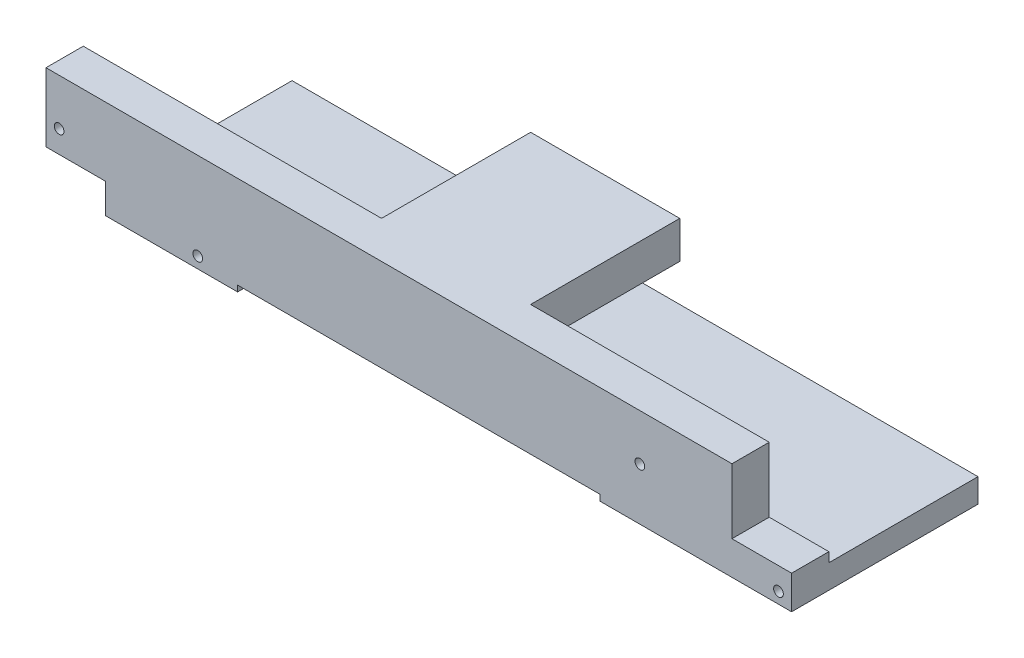
SolidWorks part; units mm, degrees
ref_plane "Front Plane" through (0, 0, 0) normal (0, 0, 1) x (1, 0, 0)
ref_plane "Top Plane" through (0, 0, 0) normal (0, 1, 0) x (1, 0, 0)
ref_plane "Right Plane" through (0, 0, 0) normal (1, 0, 0) x (0, 0, -1)
sketch "Sketch1" plane through (0, 0, 0) normal (0, 1, 0) x (1, 0, 0)
  line L1 (-63.5, -15.875) -> (63.5, -15.875)
  line L2 (-63.5, -15.875) -> (-63.5, 15.875)
  line L3 (-63.5, 15.875) -> (63.5, 15.875)
  line L4 (63.5, -15.875) -> (63.5, 15.875)
  line L5 (-63.5, -15.875) -> (63.5, 15.875) construction
  line L6 (-63.5, 15.875) -> (63.5, -15.875) construction
  point P0 (0, 0)
  dimension "D1" = 31.75
  dimension "D2" = 127
extrude "Boss-Extrude1" add sketch "Sketch1" along normal blind 16.764
sketch "Sketch2" plane through (-63.5, 0, 0) normal (-1, 0, 0) x (0, 0, 1)
  line L0 (-15.875, 16.764) -> (-15.875, 0) construction
  line L1 (-15.875, 10.414) -> (9.525, 10.414)
  line L2 (-15.875, 10.414) -> (-15.875, 4.064)
  line L3 (-15.875, 4.064) -> (9.525, 4.064)
  line L4 (9.525, 10.414) -> (9.525, 4.064)
  dimension "D1" = 6.35
  dimension "D2" = 25.4
  dimension "D3" = 4.064
extrude "Cut-Extrude1" cut sketch "Sketch2" against normal up to surface (127 mm away) up to face at (63.5, 8.382, 0)
sketch "Sketch3" plane through (-63.5, 0, 0) normal (-1, 0, 0) x (0, 0, 1)
  line L0 (9.525, 10.414) -> (-15.875, 10.414) construction
  line L1 (-15.875, 16.764) -> (9.525, 16.764)
  line L2 (-15.875, 16.764) -> (-15.875, 10.414)
  line L3 (-15.875, 10.414) -> (9.525, 10.414)
  line L4 (9.525, 16.764) -> (9.525, 10.414)
  dimension "D1" = 25.4
extrude "Cut-Extrude2" cut sketch "Sketch3" against normal blind 50.8
mirror "Mirror1" about plane through (0, 0, 0) normal (1, 0, 0) of "Cut-Extrude2"
sketch "Sketch5" plane through (0, 0, 0) normal (0, -1, 0) x (1, 0, 0)
  line L0 (-27.9908, 1.2954) -> (27.9908, 1.2954) construction
  line L1 (-63.5, 15.875) -> (63.5, 15.875) construction
  line L3 (-30.861, 15.875) -> (30.861, 15.875)
  line L4 (-30.861, 15.875) -> (-30.861, -1.2446)
  line L5 (-30.861, -1.2446) -> (30.861, -1.2446)
  line L6 (30.861, 15.875) -> (30.861, -1.2446)
  circle A0 centre (-27.9908, 1.2954) radius 0.8192
  circle A1 centre (27.9908, 1.2954) radius 0.8192
  point P0 (-27.9908, 1.2954)
  point P1 (27.9908, 1.2954)
  point P2 (0, 1.2954)
  point P12 (0, -1.2446)
  point P18 (0, -1.2446)
  line M3 (63.5, 15.875) -> (-63.5, 15.875)
  dimension "D5" = 1.6383
  dimension "D6" = 1.6383
  dimension "D1" = 2.54
  dimension "D2" = 55.9816
  dimension "D3" = 17.1196
  dimension "D4" = 61.722
extrude "Cut-Extrude3" cut sketch "Sketch5" against normal blind 1.016 contours L6 L4 L5 A0 A1 M3 | A0 | A1 region at (0, 0, 7.3393) region at (-27.9908, 0, 1.2954) region at (27.9908, 0, 1.2954)
extrude "Cut-Extrude4" cut sketch "Sketch5<3>" against normal through all contours A0 | A1 region at (-27.9908, 0, 1.2954) region at (27.9908, 0, 1.2954)
sketch "Sketch5<3>" plane through (0, 0, 0) normal (0, -1, 0) x (1, 0, 0) same geometry as "Sketch5"
sketch "Sketch6" plane through (0, 0, 15.875) normal (0, 0, 1) x (1, 0, 0)
  line L0 (-63.5, 0) -> (-30.861, 0) construction
  line L1 (-63.5, 10.7823) -> (-36.5379, 10.7823)
  line L2 (-63.5, 10.7823) -> (-63.5, 0)
  line L3 (-63.5, 0) -> (-36.5379, 0)
  line L4 (-36.5379, 10.7823) -> (-36.5379, 0)
  line L5 (-61.2648, 8.8773) -> (-37.6555, 8.8773) construction
  line L6 (-61.2648, 8.8773) -> (-61.2648, 1.905) construction
  line L7 (-61.2648, 1.905) -> (-37.6555, 1.905) construction
  line L8 (-37.6555, 8.8773) -> (-37.6555, 1.905) construction
  line L9 (-63.5, 16.764) -> (-63.5, 0) construction
  line L10 (36.5379, 10.7823) -> (63.5, 10.7823)
  line L11 (-36.5379, 10.7823) -> (-46.6979, 10.7823)
  line L12 (-36.5379, 10.7823) -> (-36.5379, 5.7023)
  line L13 (-36.5379, 5.7023) -> (-46.6979, 5.7023)
  line L14 (-46.6979, 10.7823) -> (-46.6979, 5.7023)
  line L15 (-63.5, 0) -> (-53.34, 0)
  line L16 (-63.5, 0) -> (-63.5, 5.08)
  line L17 (-63.5, 5.08) -> (-53.34, 5.08)
  line L18 (-53.34, 0) -> (-53.34, 5.08)
  line L19 (36.5379, 10.7823) -> (36.5379, 0)
  line L20 (36.5379, 0) -> (63.5, 0)
  line L21 (63.5, 10.7823) -> (63.5, 0)
  line L22 (37.6555, 8.8773) -> (61.2648, 8.8773) construction
  line L23 (37.6555, 8.8773) -> (37.6555, 1.905) construction
  line L24 (37.6555, 1.905) -> (61.2648, 1.905) construction
  line L25 (61.2648, 8.8773) -> (61.2648, 1.905) construction
  line L26 (63.5, 10.7823) -> (53.34, 10.7823)
  line L27 (63.5, 10.7823) -> (63.5, 5.7023)
  line L28 (63.5, 5.7023) -> (53.34, 5.7023)
  line L29 (53.34, 10.7823) -> (53.34, 5.7023)
  line L30 (36.5379, 0) -> (46.6979, 0)
  line L31 (36.5379, 0) -> (36.5379, 5.08)
  line L32 (36.5379, 5.08) -> (46.6979, 5.08)
  line L33 (46.6979, 0) -> (46.6979, 5.08)
  line L34 (30.861, 0) -> (63.5, 0) construction
  line L35 (63.5, 16.764) -> (63.5, 0) construction
  line L37 (53.34, 10.7823) -> (63.5, 10.7823)
  line L38 (53.34, 10.7823) -> (53.34, 16.764)
  line L39 (53.34, 16.764) -> (63.5, 16.764)
  line L40 (63.5, 10.7823) -> (63.5, 16.764)
  circle A0 centre (-61.2648, 8.8773) radius 0.8255
  circle A1 centre (-37.6555, 8.8773) radius 0.8255
  circle A2 centre (-37.6555, 1.905) radius 0.8255
  circle A3 centre (-61.2648, 1.905) radius 0.8255
  circle A4 centre (37.6555, 8.8773) radius 0.8255
  circle A5 centre (61.2648, 8.8773) radius 0.8255
  circle A6 centre (61.2648, 1.905) radius 0.8255
  circle A7 centre (37.6555, 1.905) radius 0.8255
  line M11 (63.5, 0) -> (63.5, 16.764)
  line M12 (63.5, 16.764) -> (-63.5, 16.764)
  line M14 (-63.5, 0) -> (-30.861, 0)
  dimension "D7" = 1.651
  dimension "D8" = 1.651
  dimension "D9" = 1.651
  dimension "D10" = 1.651
  dimension "D21" = 1.651
  dimension "D22" = 1.651
  dimension "D23" = 1.651
  dimension "D24" = 1.651
  dimension "D1" = 26.9621
  dimension "D2" = 10.7823
  dimension "D3" = 1.1176
  dimension "D4" = 2.2352
  dimension "D5" = 1.905
  dimension "D6" = 1.905
  dimension "D11" = 10.16
  dimension "D12" = 5.08
  dimension "D13" = 10.16
  dimension "D14" = 5.08
  dimension "D15" = 26.9621
  dimension "D16" = 10.7823
  dimension "D17" = 1.1176
  dimension "D18" = 2.2352
  dimension "D19" = 1.905
  dimension "D20" = 1.905
  dimension "D25" = 10.16
  dimension "D26" = 5.08
  dimension "D27" = 10.16
  dimension "D28" = 5.08
extrude "Cut-Extrude8" cut sketch "Sketch6" against normal up to surface (31.75 mm away) contours A5 | L10 L29 L28 L21 A5 | A4 | A6 | L18 L17 L2 A3 M14 | A3 | A2 | A0 | L38 L10 M11 M12 region at (-58.2969, 2.5675, 15.875) region at (58.42, 13.7732, 15.875) region at (58.2969, 8.2148, 15.875) region at (-61.2648, 8.8773, 15.875) region at (-37.6555, 1.905, 15.875) region at (-61.2648, 1.905, 15.875) region at (37.6555, 8.8773, 15.875) region at (61.2648, 8.8773, 15.875) region at (61.2648, 1.905, 15.875) up to face at (0, 2.032, -15.875)
